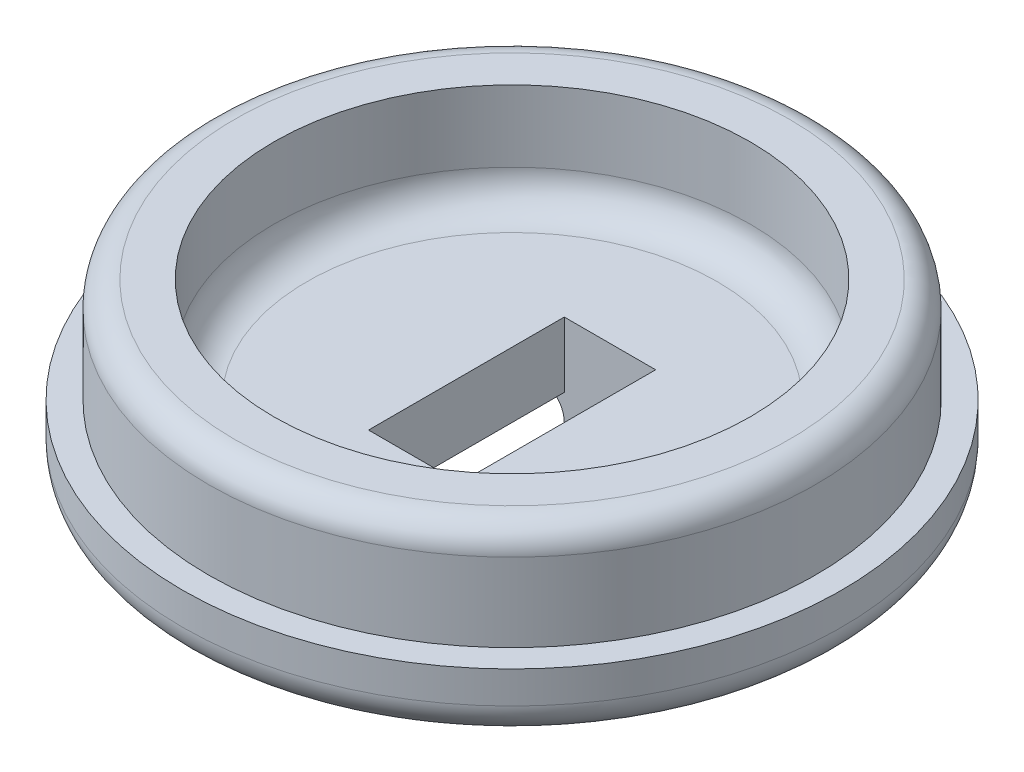
SolidWorks part; units mm, degrees
ref_plane "Front Plane" through (0, 0, 0) normal (0, 0, 1) x (1, 0, 0)
ref_plane "Top Plane" through (0, 0, 0) normal (0, 1, 0) x (1, 0, 0)
ref_plane "Right Plane" through (0, 0, 0) normal (1, 0, 0) x (0, 0, -1)
sketch "Sketch1" plane through (0, 0, 0) normal (0, 1, 0) x (1, 0, 0)
  circle A0 centre (0, 0) radius 25.25
  dimension "D1" = 50.5
extrude "Boss-Extrude1" add sketch "Sketch1" along normal blind 5
sketch "Sketch2" plane through (0, 5, 0) normal (0, 1, 0) x (1, 0, 0)
  circle A0 centre (0, 0) radius 23.25
  circle A1 centre (0, 0) radius 18.25
  dimension "D1" = 46.5
  dimension "D2" = 36.5
extrude "Boss-Extrude2" add sketch "Sketch2" along normal blind 8
fillet "Fillet1" radius 2.54 2 edges at (0, 5, 18.25) (0, 0, 25.25)
fillet "Fillet3" radius 2 1 edges at (0, 13, 23.25)
sketch "Sketch3" plane through (0, 0, 0) normal (0, -1, 0) x (-1, 0, 0)
  line L1 (-3.5, 7.5) -> (3.5, 7.5)
  line L2 (-3.5, 7.5) -> (-3.5, -7.5)
  line L3 (-3.5, -7.5) -> (3.5, -7.5)
  line L4 (3.5, 7.5) -> (3.5, -7.5)
  line L5 (-3.5, 7.5) -> (3.5, -7.5) construction
  line L6 (-3.5, -7.5) -> (3.5, 7.5) construction
  line L7 (-3.5, -7.5) -> (3.5, -7.5)
  line L8 (-3.5, -7.5) -> (-3.5, -10.5)
  line L9 (-3.5, -10.5) -> (3.5, -10.5)
  line L10 (3.5, -7.5) -> (3.5, -10.5)
  line L11 (-3.5, 7.5) -> (3.5, 7.5)
  line L12 (-3.5, 7.5) -> (-3.5, 10.5)
  line L13 (-3.5, 10.5) -> (3.5, 10.5)
  line L14 (3.5, 7.5) -> (3.5, 10.5)
  point P0 (0, 0)
  dimension "D1" = 15
  dimension "D2" = 7
  dimension "D3" = 3
  dimension "D4" = 3
extrude "Cut-Extrude1" cut sketch "Sketch3" against normal through all contours L4 L1 L2 L3 region at (0, 0, 0)
sketch "Sketch4" plane through (0, 0, 0) normal (0, -1, 0) x (-1, 0, 0)
  line L1 (-3.5, 7.5) -> (3.5, 7.5)
  line L2 (-3.5, 7.5) -> (-3.5, 10.5)
  line L3 (-3.5, 10.5) -> (3.5, 10.5)
  line L4 (3.5, 7.5) -> (3.5, 10.5)
  line L5 (-3.5, -7.5) -> (3.5, -7.5)
  line L6 (-3.5, -7.5) -> (-3.5, -10.5)
  line L7 (-3.5, -10.5) -> (3.5, -10.5)
  line L8 (3.5, -7.5) -> (3.5, -10.5)
  dimension "D1" = 3
  dimension "D2" = 3
extrude "Boss-Extrude3" add sketch "Sketch4" along normal blind 4
sketch "Sketch5" plane through (0, -4, 0) normal (0, -1, 0) x (-1, 0, 0)
  line L1 (-3.5, 10.5) -> (3.5, 10.5)
  line L2 (-3.5, 10.5) -> (-3.5, -10.5)
  line L3 (-3.5, -10.5) -> (3.5, -10.5)
  line L4 (3.5, 10.5) -> (3.5, -10.5)
extrude "Boss-Extrude4" add sketch "Sketch5" along normal blind 2
fillet "Fillet4" radius 2 2 edges at (0, 0, -10.5) (0, 0, 10.5)
fillet "Fillet5" radius 1 2 edges at (0, -4, 7.5) (0, -4, -7.5)
fillet "Fillet6" radius 2 4 edges at (-3.5, 0, 10) (-3.5, 0, -10) (3.5, 0, -10) (3.5, 0, 10)
